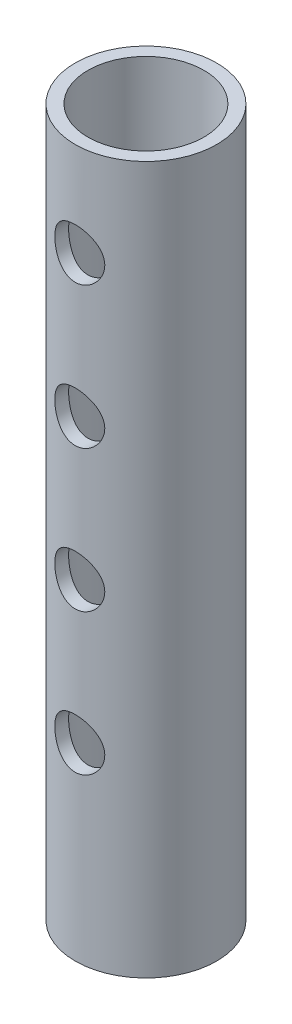
SolidWorks part; units mm, degrees
material "ABS"
ref_plane "前视基准面" through (0, 0, 0) normal (0, 0, 1) x (1, 0, 0)
ref_plane "上视基准面" through (0, 0, 0) normal (0, 1, 0) x (1, 0, 0)
ref_plane "右视基准面" through (0, 0, 0) normal (1, 0, 0) x (0, 0, -1)
other "Configuration Table"
sketch "草图1" plane through (0, 0, 0) normal (0, 1, 0) x (1, 0, 0)
  circle A0 centre (0, 0) radius 6.15
  circle A1 centre (0, 0) radius 7.5
  dimension "D1" = 12.3
  dimension "D2" = 15
extrude "凸台-拉伸1" add sketch "草图1" along normal blind 75 contours A1 A0 region at (-7.2879, 0, 0)
sketch "草图3" plane through (0, 0, 0) normal (0, 0, 1) x (1, 0, 0)
  circle A0 centre (0, 20) radius 2.65 construction
  circle A1 centre (0, 35) radius 2.65 construction
  circle A2 centre (0, 50) radius 2.65 construction
  circle A3 centre (0, 65) radius 2.65 construction
  circle A4 centre (0, 20) radius 2.65
  circle A5 centre (0, 35) radius 2.65
  circle A6 centre (0, 50) radius 2.65
  circle A7 centre (0, 65) radius 2.65
extrude "切除-拉伸1" cut sketch "草图3" against normal through all and the other way through all
